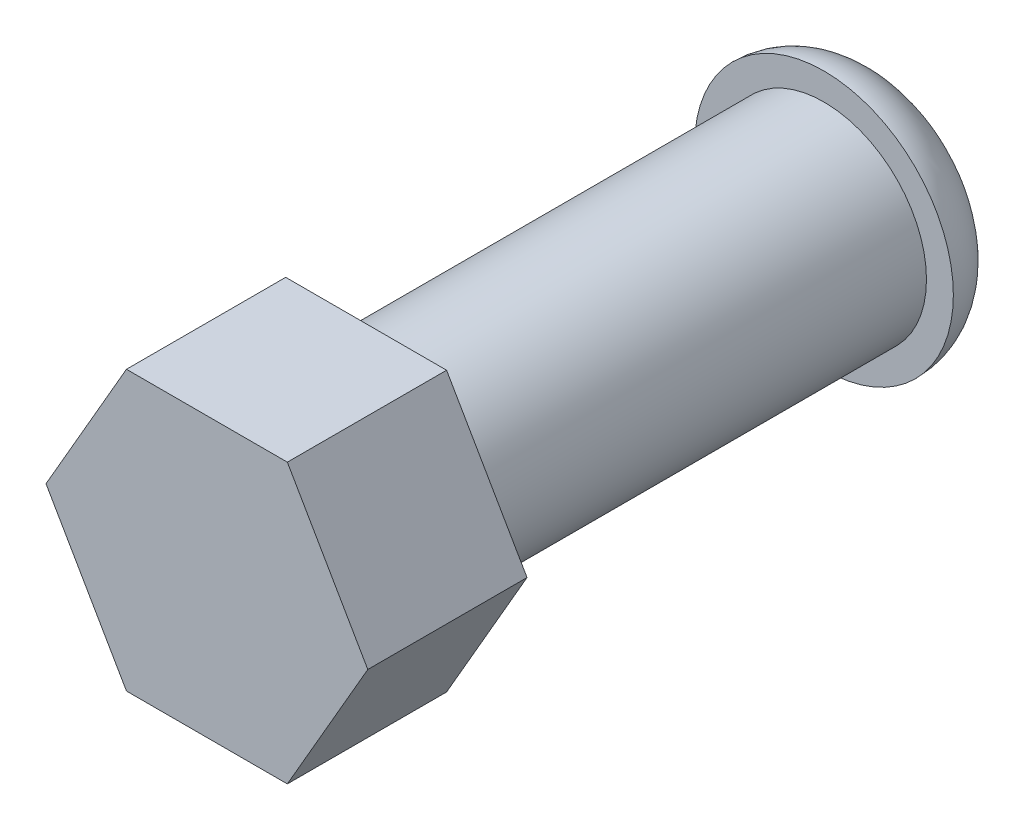
SolidWorks part; units mm, degrees
material "AISI 1045 Acero estirado en frío"
ref_plane "Alzado" through (0, 0, 0) normal (0, 0, 1) x (1, 0, 0)
ref_plane "Planta" through (0, 0, 0) normal (0, 1, 0) x (1, 0, 0)
ref_plane "Vista lateral" through (0, 0, 0) normal (1, 0, 0) x (0, 0, -1)
sketch "Croquis1" plane through (0, 0, 0) normal (0, 0, 1) x (1, 0, 0)
  circle A0 centre (0, 0) radius 5.15
  dimension "D1" = 10.3
extrude "Saliente-Extruir1" add sketch "Croquis1" along normal blind 23
sketch "Croquis2" plane through (0, 0, 23) normal (0, 0, 1) x (1, 0, 0)
  line L1 (8.0829, 0) -> (4.0415, 7)
  line L2 (4.0415, 7) -> (-4.0415, 7)
  line L3 (-4.0415, 7) -> (-8.0829, 0)
  line L4 (-8.0829, 0) -> (-4.0415, -7)
  line L5 (-4.0415, -7) -> (4.0415, -7)
  line L6 (4.0415, -7) -> (8.0829, 0)
  circle A0 centre (0, 0) radius 7 construction
extrude "Saliente-Extruir2" add sketch "Croquis2" along normal blind 8
sketch "Croquis3" plane through (0, 0, 0) normal (0, 0, -1) x (-1, 0, 0)
  circle A0 centre (0, 0) radius 6.5
  dimension "D1" = 13
extrude "Saliente-Extruir3" add sketch "Croquis3" along normal blind 3
fillet "Redondeo1" radius 3 1 edges at (-6.5, 0, -3)
